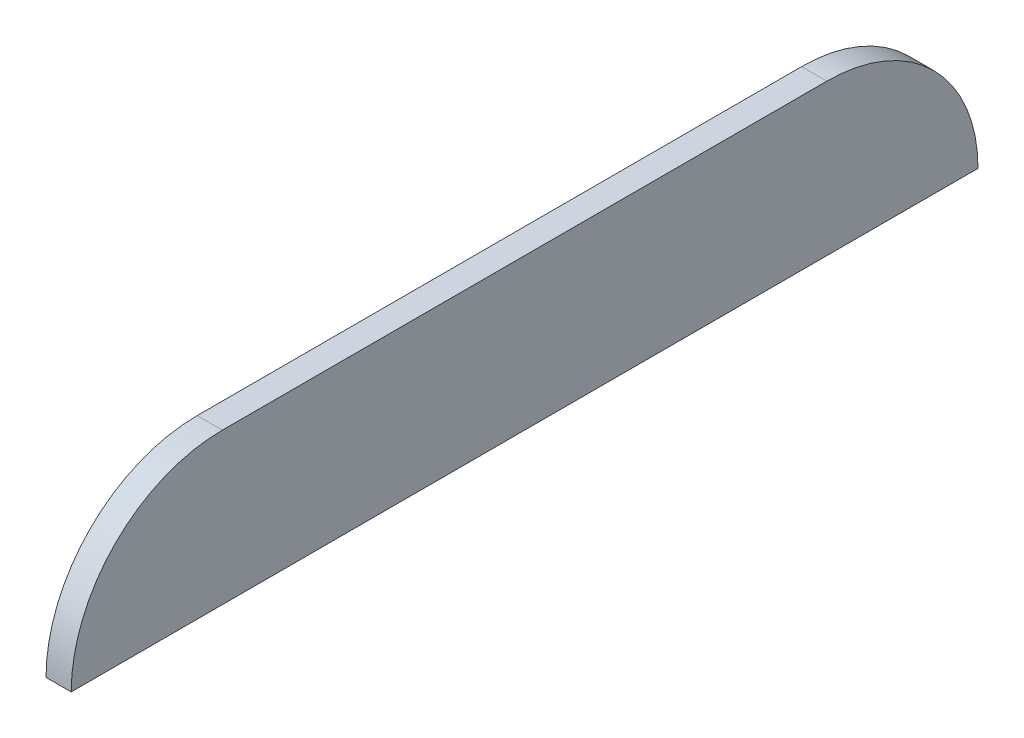
SolidWorks part; units mm, degrees
ref_plane "Front Plane" through (0, 0, 0) normal (0, 0, 1) x (1, 0, 0)
ref_plane "Top Plane" through (0, 0, 0) normal (0, 1, 0) x (1, 0, 0)
ref_plane "Right Plane" through (0, 0, 0) normal (1, 0, 0) x (0, 0, -1)
sketch "Sketch1" plane through (0, 0, 0) normal (1, 0, 0) x (0, 0, -1)
  line L0 (0, 61.8017) -> (0, -66.4535) construction
  line L1 (-118.9517, 0) -> (106.9901, 0) construction
  line L3 (-57.15, 9.525) -> (57.15, 9.525)
  line L4 (-57.15, 9.525) -> (-57.15, -9.525)
  line L5 (-57.15, -9.525) -> (57.15, -9.525)
  line L6 (57.15, 9.525) -> (57.15, -9.525)
  dimension "D1" = 114.3
  dimension "D2" = 19.05
extrude "Boss-Extrude1" add sketch "Sketch1" along normal blind 3.175
fillet "Fillet1" radius 19.05 2 edges at (1.5875, 9.525, -57.15) (1.5875, 9.525, 57.15)
